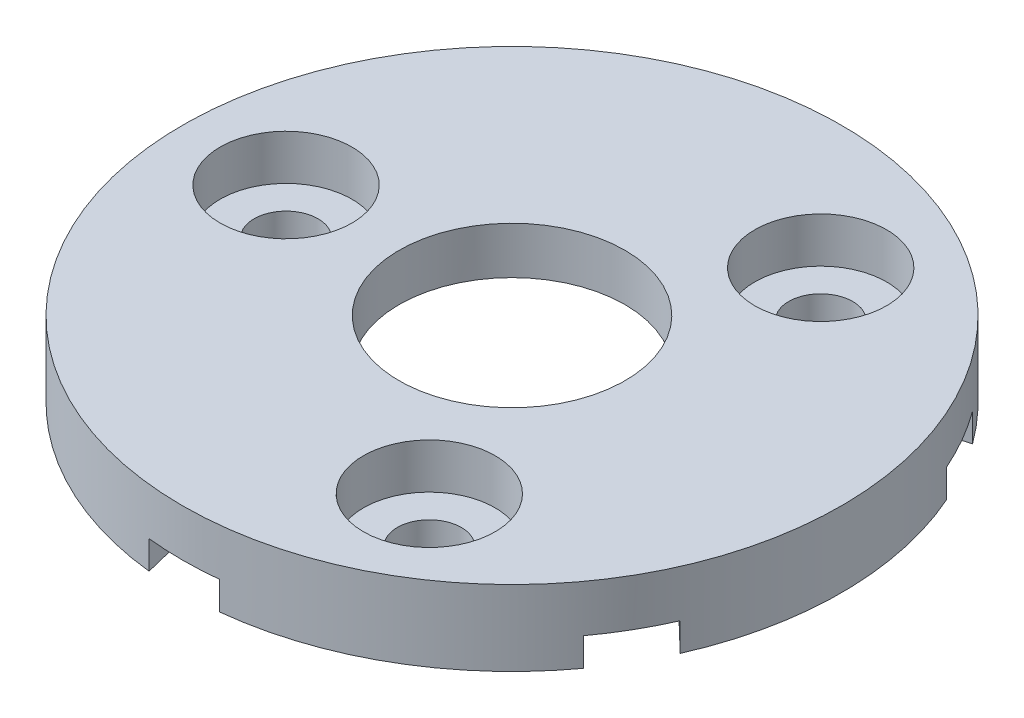
SolidWorks part; units mm, degrees
ref_plane "Front Plane" through (0, 0, 0) normal (0, 0, 1) x (1, 0, 0)
ref_plane "Top Plane" through (0, 0, 0) normal (0, 1, 0) x (1, 0, 0)
ref_plane "Right Plane" through (0, 0, 0) normal (1, 0, 0) x (0, 0, -1)
sketch "Sketch1" plane through (0, 0, 0) normal (0, 1, 0) x (1, 0, 0)
  circle A0 centre (0, 0) radius 17.5
  dimension "D1" = 35
extrude "Boss-Extrude1" add sketch "Sketch1" along normal blind 4
hole_wizard "CBORE for M3 Pan Head Screw1" positions "Sketch3" profile "Sketch2" counterbore size "M3" standard "ISO" end condition through all
sketch "Sketch3" plane through (0, 4, 0) normal (0, 1, 0) x (1, 0, 0)
  point P0 (-12, 0)
  dimension "D1" = 12
sketch "Sketch2" plane through (-12, 4, 0) normal (1, 0, 0) x (0, 0, 1)
  line L0 (0, 0) -> (0, 4)
  line L1 (0, 4) -> (1.7, 4)
  line L3 (1.7, 4) -> (1.7, 2.4)
  line L4 (1.7, 2.4) -> (3.5, 2.4)
  line L5 (3.5, 2.4) -> (3.5, 0)
  line L7 (3.5, 0) -> (0, 0)
  line L11 (0, -6.35) -> (0, 107.95) construction
  dimension "Thru Hole Dia." = 3.4
  dimension "Thru Hole Depth" = 4
  dimension "C'Bore Dia." = 7
  dimension "C'Bore Depth" = 2.4
pattern_circular "CirPattern1" count 3 over 360 about axis through (0, 4, 0) along (0, -1, 0) of "CBORE for M3 Pan Head Screw1"
hole_wizard "Ø12.0 (12) Diameter Hole1" positions "Sketch5" profile "Sketch6" hole size "Ø12.0" standard "ISO" end condition through all
sketch "Sketch5" plane through (0, 0, 0) normal (0, -1, 0) x (-1, 0, 0)
  point P0 (0, 0)
sketch "Sketch6" plane through (0, 0, 0) normal (1, 0, 0) x (0, 0, -1)
  line L0 (0, 0) -> (0, 4)
  line L1 (0, 4) -> (6, 4)
  line L2 (6, 4) -> (6, 0)
  line L5 (6, 0) -> (0, 0)
  line L11 (0, -6.35) -> (0, 107.95) construction
  dimension "Thru Hole Dia." = 12
  dimension "Thru Hole Depth" = 4
sketch "Sketch7" plane through (0, 0, 0) normal (0, -1, 0) x (1, 0, 0)
  line L0 (0, 0) -> (0, 25) construction
  line L1 (0, 25) -> (-5.7236, 1.8)
  line L2 (-5.7236, 1.8) -> (5.7236, 1.8)
  line L3 (5.7236, 1.8) -> (0, 25)
  circle A0 centre (0, 0) radius 6 construction
  dimension "D1" = 25
extrude "Cut-Extrude1" cut sketch "Sketch7" against normal blind 1.5
pattern_circular "CirPattern2" count 6 over 360 about axis through (0, 0, 0) along (0, -1, 0) of "Cut-Extrude1"
